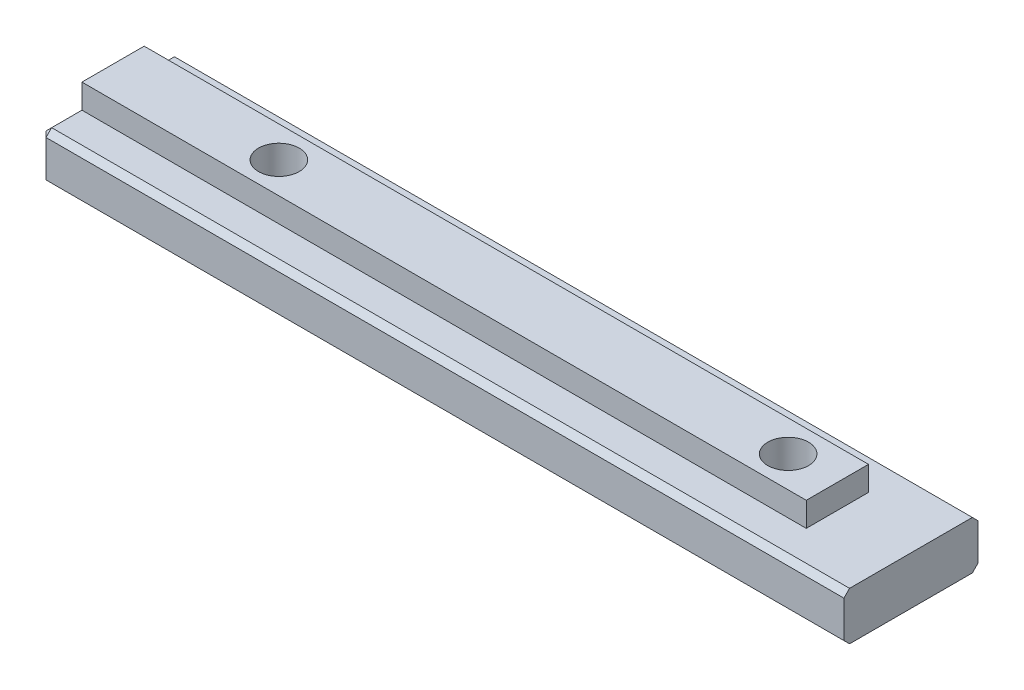
SolidWorks part; units mm, degrees
ref_plane "Front Plane" through (0, 0, 0) normal (0, 0, 1) x (1, 0, 0)
ref_plane "Top Plane" through (0, 0, 0) normal (0, 1, 0) x (1, 0, 0)
ref_plane "Right Plane" through (0, 0, 0) normal (1, 0, 0) x (0, 0, -1)
sketch "Sketch1" plane through (0, 0, 0) normal (0, 1, 0) x (1, 0, 0)
  line L1 (-32.5, 5.925) -> (32.5, 5.925)
  line L2 (-32.5, 5.925) -> (-32.5, -5.925)
  line L3 (-32.5, -5.925) -> (32.5, -5.925)
  line L4 (32.5, 5.925) -> (32.5, -5.925)
  line L5 (-32.5, 5.925) -> (32.5, -5.925) construction
  line L6 (-32.5, -5.925) -> (32.5, 5.925) construction
  point P0 (0, 0)
  dimension "D1" = 11.85
  dimension "D2" = 65
extrude "Boss-Extrude1" add sketch "Sketch1" along normal blind 4.25
sketch "Sketch2" plane through (0, 0, 0) normal (0, -1, 0) x (1, 0, 0)
  line L0 (-17.3502, 0) -> (27.6498, 0) construction
  point P3 (5.1498, 0)
  point P4 (0, 0)
  point P5 (-17.3502, 0)
  point P6 (27.6498, 0)
  point P8 (-17.4991, 0)
  point P9 (-19.0812, -1.9169)
  dimension "D1" = 45
  dimension "D2" = 1.731
chamfer "Chamfer1" distance 0.5 angle 45 8 edges at (0, 4.25, 5.925) (-32.5, 4.25, 0) (0, 4.25, -5.925) (0, 0, 5.925) (0, 0, -5.925) (-32.5, 2.125, 5.925) (-32.5, 2.125, -5.925) (-32.5, 0, 0)
sketch "Sketch7" plane through (0, 0, 0) normal (1, 0, 0) x (0, 0, -1)
  line L1 (-2.75, 4.25) -> (2.75, 4.25)
  line L2 (-2.75, 4.25) -> (-2.75, 6.4)
  line L3 (-2.75, 6.4) -> (2.75, 6.4)
  line L4 (2.75, 4.25) -> (2.75, 6.4)
  line L6 (-5.425, 4.25) -> (5.425, 4.25) construction
  point P7 (0, 4.25)
  point P8 (0, 4.25)
  dimension "D1" = 5.5
  dimension "D2" = 2.15
extrude "Boss-Extrude2" add sketch "Sketch7" along normal up to vertex (-32 mm away) and the other way up to vertex (32 mm away) up to point (-32, 4.25, 5.425) other way up to point (-32, 4.25, 5.425)
hole_wizard "CBORE for M3 SHCS1" positions "Sketch5" profile "Sketch6" counterbore size "M3" standard "ANSI Metric" end condition through all
sketch "Sketch5" plane through (0, 0, 0) normal (0, -1, 0) x (-1, 0, 0)
  point P0 (-27.6498, 0)
  point P3 (17.3502, 0)
sketch "Sketch6" plane through (27.6498, 0, 0) normal (1, 0, 0) x (0, 0, -1)
  line L0 (0, 0) -> (0, 6.4)
  line L1 (0, 6.4) -> (1.8, 6.4)
  line L3 (1.8, 6.4) -> (1.8, 2.2)
  line L4 (3.25, 2.2) -> (1.8, 2.2)
  line L5 (3.25, 2.2) -> (3.25, 0.025)
  line L6 (3.25, 0.025) -> (3.275, 0)
  line L7 (3.275, 0) -> (0, 0)
  line L8 (-3.25, 0.025) -> (-3.275, 0) construction
  line L11 (0, -6.35) -> (0, 107.95) construction
  dimension "Thru Hole Dia." = 3.6
  dimension "Thru Hole Depth" = 6.4
  dimension "C'Bore Dia." = 6.5
  dimension "C'Bore Depth" = 2.2
  dimension "Near C'Sink Dia." = 6.55
  dimension "Near C'Sink Angle" = 90
sketch "Sketch8" plane through (32.5, 0, 0) normal (1, 0, 0) x (0, 0, -1)
  line L8 (5.425, 4.25) -> (-5.425, 4.25)
  line L9 (-5.425, 4.25) -> (-5.925, 3.75)
  line L10 (-5.925, 3.75) -> (-5.925, 0.5)
  line L11 (-5.925, 0.5) -> (-5.425, 0)
  line L12 (-5.425, 0) -> (5.425, 0)
  line L14 (5.425, 4.25) -> (-5.425, 4.25)
  line L17 (-5.425, 4.25) -> (-5.925, 3.75)
  line L18 (-5.925, 3.75) -> (-5.925, 0.5)
  line L19 (-5.925, 0.5) -> (-5.425, 0)
  line L20 (-5.425, 0) -> (5.425, 0)
  line L24 (5.425, 0) -> (5.925, 0.5)
  line L25 (5.425, 0) -> (5.925, 0.5)
  line L27 (5.925, 0.5) -> (5.925, 3.75)
  line L29 (5.925, 0.5) -> (5.925, 3.75)
  line L31 (5.925, 3.75) -> (5.425, 4.25)
  line L32 (5.925, 3.75) -> (5.425, 4.25)
  dimension "D1" = 0
extrude "Boss-Extrude3" add sketch "Sketch8" along normal blind 6
sketch "Sketch10" plane through (0, 0, 0) normal (0, 0, 1) x (1, 0, 0)
  line L1 (33.15, 0) -> (36.45, 0)
  line L2 (33.15, 0) -> (33.15, 2.5)
  line L3 (33.15, 2.5) -> (36.45, 2.5)
  line L4 (36.45, 0) -> (36.45, 2.5)
  line L6 (38.5, 0) -> (-32, 0) construction
  line L7 (33.35, -0.5) -> (33.35, 1.7) construction
  point P4 (34.45, 0)
  point P6 (40.8884, 2.5)
  dimension "D1" = 0.2
  dimension "D2" = 2.5
  dimension "D3" = 3.3
extrude "Cut-Extrude1" cut sketch "Sketch10" against normal blind 2 and the other way blind 2
